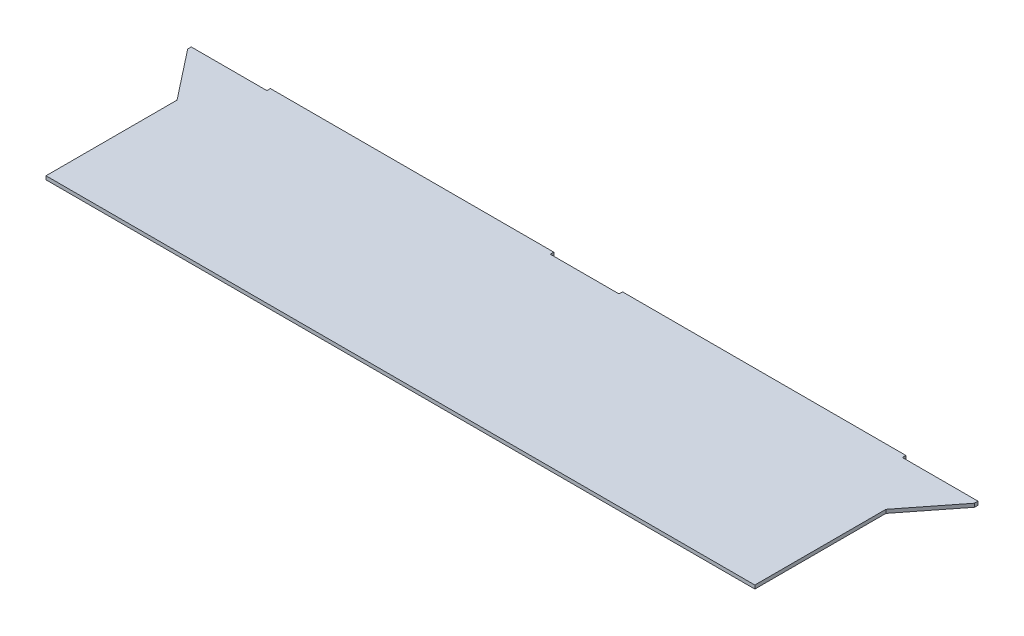
SolidWorks part; units mm, degrees
material "6061-T6 (SS)"
ref_plane "X-Y Datum" through (0, 0, 0) normal (0, 0, 1) x (1, 0, 0)
ref_plane "X-Z Datum" through (0, 0, 0) normal (0, 1, 0) x (1, 0, 0)
ref_plane "Y-Z Datum" through (0, 0, 0) normal (1, 0, 0) x (0, 0, -1)
sketch "Sketch1" plane through (0, 0, 0) normal (0, 1, 0) x (1, 0, 0)
  line L1 (-317.6778, 82.55) -> (317.6778, 82.55)
  line L2 (-317.6778, 82.55) -> (-317.6778, -82.55)
  line L3 (-317.6778, -82.55) -> (317.6778, -82.55)
  line L4 (317.6778, 82.55) -> (317.6778, -82.55)
  line L5 (-317.6778, 82.55) -> (317.6778, -82.55) construction
  line L6 (-317.6778, -82.55) -> (317.6778, 82.55) construction
  point P0 (0, 0)
  dimension "D1" = 635.3556
  dimension "D2" = 165.1
extrude "Boss-Extrude1" add sketch "Sketch1" along normal mid plane 3.175
sketch "Sketch2" plane through (0, 0, -82.55) normal (0, 0, -1) x (-1, 0, 0)
  line L20 (-317.6778, -1.5875) -> (317.6778, -1.5875) construction
  line L21 (-284.8229, -1.5875) -> (-30.8229, -1.5875)
  line L22 (30.8229, -1.5875) -> (284.8229, -1.5875)
  line L40 (30.8229, -1.5875) -> (30.8229, 1.5875)
  line L41 (30.8229, 1.5875) -> (284.8229, 1.5875)
  line L42 (284.8229, 1.5875) -> (284.8229, -1.5875)
  line L56 (-284.8229, -1.5875) -> (-284.8229, 1.5875)
  line L57 (-284.8229, 1.5875) -> (-30.8229, 1.5875)
  line L58 (-30.8229, 1.5875) -> (-30.8229, -1.5875)
extrude "Boss-Extrude2" add sketch "Sketch2" along normal blind 3.175
sketch "Sketch3" plane through (0, -1.5875, 0) normal (0, -1, 0) x (1, 0, 0)
  line L0 (317.6778, -82.55) -> (352.6028, -82.55)
  line L1 (352.6028, -82.55) -> (352.6028, -79.375)
  line L3 (352.6028, -79.375) -> (317.6778, -34.925)
  line L4 (317.6778, 82.55) -> (317.6778, -82.55) construction
  line L17 (317.6778, -82.55) -> (317.6778, 82.55)
  line L18 (317.6778, 82.55) -> (-317.6778, 82.55)
  line L19 (-317.6778, 82.55) -> (-317.6778, -82.55)
  line L20 (-317.6778, -82.55) -> (-284.8229, -82.55)
  line L21 (-284.8229, -82.55) -> (-284.8229, -85.725)
  line L22 (-284.8229, -85.725) -> (-30.8229, -85.725)
  line L23 (-30.8229, -85.725) -> (-30.8229, -82.55)
  line L24 (-30.8229, -82.55) -> (30.8229, -82.55)
  line L25 (30.8229, -82.55) -> (30.8229, -85.725)
  line L26 (30.8229, -85.725) -> (284.8229, -85.725)
  line L27 (284.8229, -85.725) -> (284.8229, -82.55)
  line L28 (284.8229, -82.55) -> (317.6778, -82.55)
  line L29 (317.6778, -82.55) -> (317.6778, -34.925)
  dimension "D1" = 34.925
  dimension "D2" = 3.175
  dimension "D3" = 44.45
  dimension "D4" = 0
extrude "Boss-Extrude3" add sketch "Sketch3" against normal blind 3.175
mirror "Mirror1" about plane through (0, 0, 0) normal (1, 0, 0) of "Boss-Extrude3"
